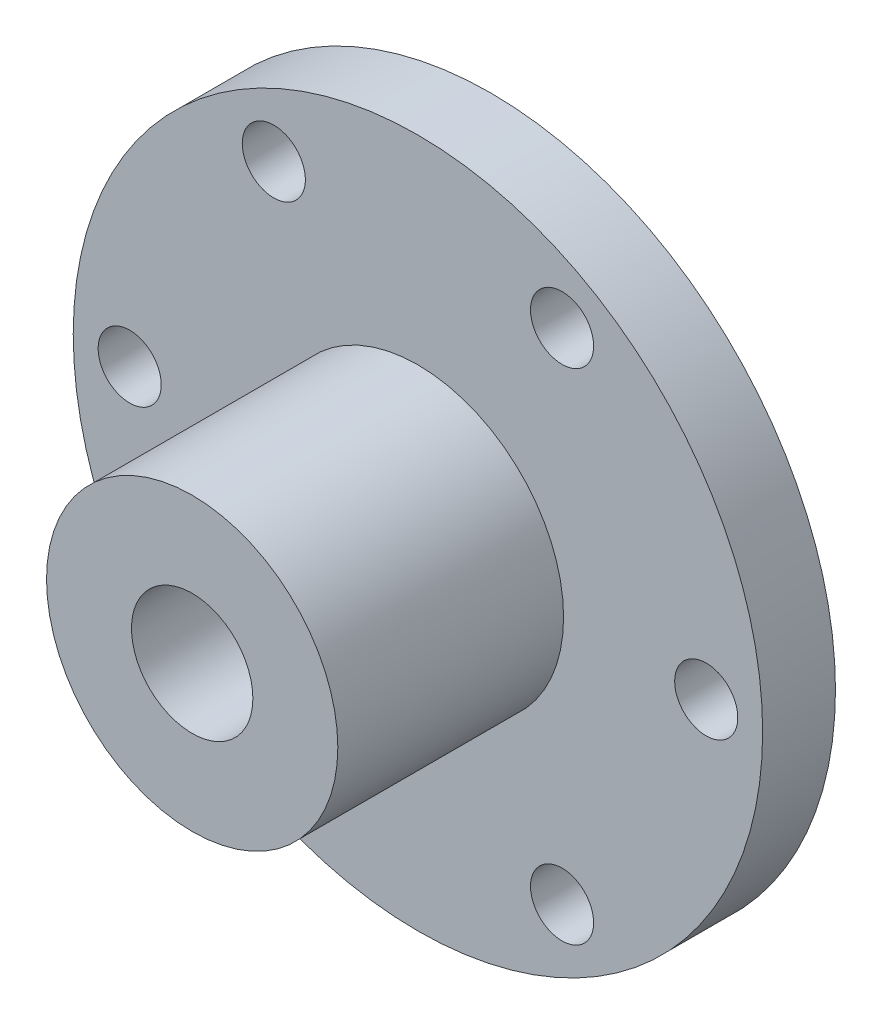
SolidWorks part; units mm, degrees
material "6061 Alloy"
ref_plane "Front Plane" through (0, 0, 0) normal (0, 0, 1) x (1, 0, 0)
ref_plane "Top Plane" through (0, 0, 0) normal (0, 1, 0) x (1, 0, 0)
ref_plane "Right Plane" through (0, 0, 0) normal (1, 0, 0) x (0, 0, -1)
sketch "Sketch1" plane through (0, 0, 0) normal (0, 1, 0) x (1, 0, 0)
  line L0 (0, 0) -> (0, 24.6) construction
  line L1 (-5, 24.6) -> (-28.4, 24.6)
  line L2 (-28.4, 24.6) -> (-28.4, 18.6)
  line L3 (-28.4, 18.6) -> (-12, 18.6)
  line L4 (-12, 18.6) -> (-12, 0)
  line L5 (-12, 0) -> (-5, 0)
  line L6 (-5, 0) -> (-5, 24.6)
  point P8 (0, 24.6)
  point P10 (0, 0)
  dimension "D1" = 5
  dimension "D2" = 24.6
  dimension "D3" = 6
  dimension "D4" = 12
  dimension "D5" = 28.4
revolve "Revolve1" add sketch "Sketch1" angle 360 about L0
sketch "Sketch2" plane through (0, 0, -24.6) normal (0, 0, -1) x (-1, 0, 0)
  line L0 (-23.75, 0) -> (0, 0) construction
  circle A0 centre (-23.75, 0) radius 2.6
  circle A1 centre (-11.875, 20.5681) radius 2.6
  circle A2 centre (11.875, 20.5681) radius 2.6
  circle A3 centre (23.75, 0) radius 2.6
  circle A4 centre (11.875, -20.5681) radius 2.6
  circle A5 centre (-11.875, -20.5681) radius 2.6
  point P16 (0, 0)
  dimension "D1" = 5.2
  dimension "D2" = 23.75
  dimension "D3" = 6
extrude "Cut-Extrude1" cut sketch "Sketch2" against normal through all
sketch "Sketch3" plane through (0, 0, 0) normal (0, 1, 0) x (1, 0, 0)
  line L0 (-12, 0) -> (12, 0) construction
  circle A0 centre (0, 10.2) radius 2.75
  dimension "D2" = 5.5
  dimension "D1" = 10.2
extrude "Cut-Extrude2" cut sketch "Sketch3" against normal up to next
